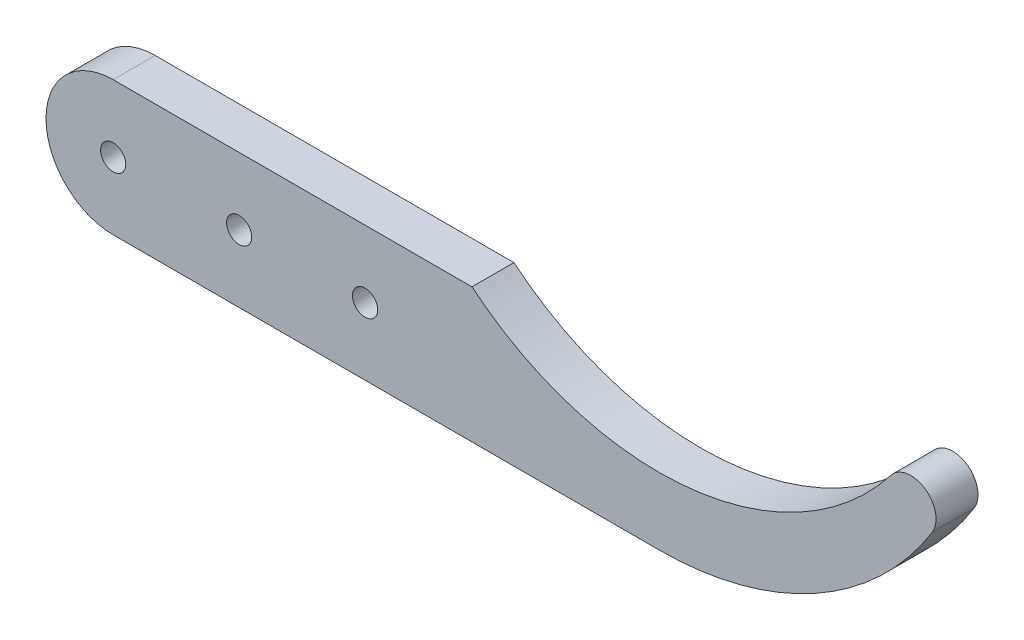
SolidWorks part; units mm, degrees
ref_plane "Plan de face" through (0, 0, 0) normal (0, 0, 1) x (1, 0, 0)
ref_plane "Plan de dessus" through (0, 0, 0) normal (0, 1, 0) x (1, 0, 0)
ref_plane "Plan de droite" through (0, 0, 0) normal (1, 0, 0) x (0, 0, -1)
sketch "Esquisse1" plane through (0, 0, 0) normal (0, 0, 1) x (1, 0, 0)
  line L0 (0, 0) -> (80, 0) construction
  line L1 (20, 0) -> (20, 23.8674) construction
  line L2 (0, 0) -> (0, 35) construction
  line L3 (0, 35) -> (50, 35) construction
  line L4 (0, 8) -> (20, 8)
  line L5 (77.6316, 13.5175) -> (80, 11.6762) construction
  line L6 (20, 8) -> (27.7289, 8)
  line L7 (0, -8) -> (50, -8)
  line L8 (50, 35) -> (50, -8) construction
  line L9 (0, 8) -> (-15, 8)
  line L10 (0, 0) -> (-15, 0) construction
  line L11 (0, -8) -> (-15, -8)
  circle A0 centre (0, 0) radius 1.5
  arc A1 (0, 8) -> (0, -8) centre (0, 0) ccw construction
  circle A2 centre (50, 35) radius 35 construction
  arc A3 (27.7289, 8) -> (77.6316, 13.5175) centre (50, 35) ccw
  arc A4 (77.6316, 13.5175) -> (82.5479, 10.0925) centre (80, 11.6762) cw
  arc A5 (50, -8) -> (82.5479, 10.0925) centre (50, 30.3227) ccw
  circle A6 centre (15, 0) radius 1.5
  arc A7 (-15, 8) -> (-15, -8) centre (-15, 0) ccw
  circle A8 centre (-15, 0) radius 1.5
  dimension "D3" = 3
  dimension "D4" = 35
  dimension "D6" = 70
  dimension "D7" = 3
  dimension "D8" = 8
  dimension "D9" = 30
  dimension "D10" = 15
  dimension "D11" = 8
  dimension "D1" = 20
  dimension "D2" = 80
  dimension "D5" = 50
  dimension "D12" = 15
extrude "Boss.-Extru.1" add sketch "Esquisse1" along normal blind 5
